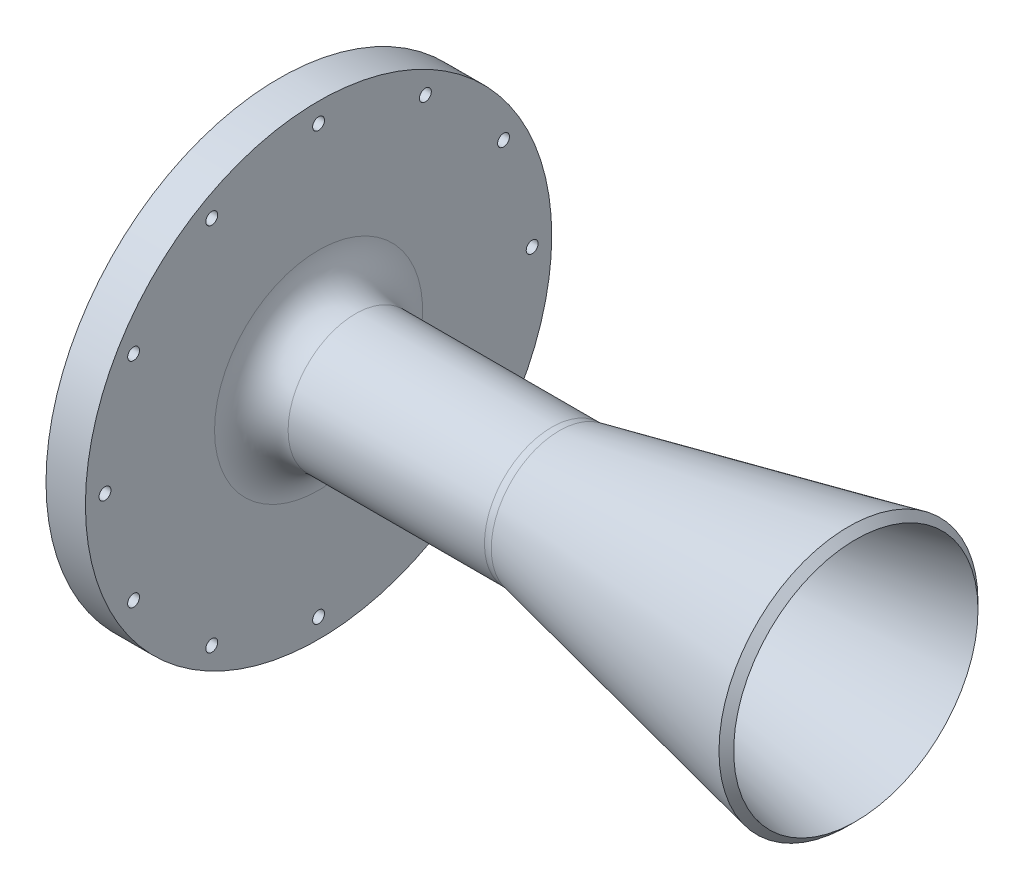
SolidWorks part; units mm, degrees
material "Stainless Steel (ferritic)"
ref_plane "Front Plane" through (0, 0, 0) normal (0, 0, 1) x (1, 0, 0)
ref_plane "Top Plane" through (0, 0, 0) normal (0, 1, 0) x (1, 0, 0)
ref_plane "Right Plane" through (0, 0, 0) normal (1, 0, 0) x (0, 0, -1)
sketch "Sketch2" plane through (0, 0, 0) normal (0, 0, 1) x (1, 0, 0)
  line L0 (0, 0) -> (165.0115, 0) construction
  line L1 (0, 20.5835) -> (0, 56.3562)
  line L2 (0, 56.3562) -> (9.525, 56.3562)
  line L3 (9.525, 56.3562) -> (9.525, 16.256)
  line L11 (66.8065, 16.256) -> (139.7, 31.75)
  line L17 (139.7, 31.75) -> (139.7, 29.5925)
  line L18 (60.325, 12.7208) -> (60.325, 14.351)
  line L19 (60.325, 14.351) -> (10.795, 14.351)
  line L20 (0, 20.5835) -> (10.795, 14.351)
  line L21 (60.325, 12.7208) -> (139.7, 29.5925)
  line L22 (9.525, 16.256) -> (66.8065, 16.256)
  dimension "D2" = 9.525
  dimension "D3" = 1.905
  dimension "D4" = 10.795
  dimension "D5" = 14.351
  dimension "D6" = 31.75
  dimension "D7" = 12
  dimension "D8" = 139.7
  dimension "D9" = 1.6302
  dimension "D10" = 30
  dimension "D11" = 56.3562
  dimension "D12" = 49.53
revolve "Main Structure" add sketch "Sketch2" angle 360 about L0
sketch "Sketch4" plane through (0, 0, 0) normal (-1, 0, 0) x (0, 0, 1)
  circle A0 centre (0, 0) radius 51.6255 construction
  circle A1 centre (0, -51.6255) radius 2.146
  circle A2 centre (-25.8127, -44.709) radius 2.146
  circle A3 centre (-44.709, -25.8128) radius 2.146
  circle A4 centre (-51.6255, 0) radius 2.146
  circle A5 centre (-44.709, 25.8127) radius 2.146
  circle A6 centre (-25.8128, 44.709) radius 2.146
  circle A7 centre (0, 51.6255) radius 2.146
  circle A8 centre (25.8127, 44.709) radius 2.146
  circle A9 centre (44.709, 25.8128) radius 2.146
  circle A10 centre (51.6255, 0) radius 2.146
  circle A11 centre (44.709, -25.8127) radius 2.146
  circle A12 centre (25.8128, -44.709) radius 2.146
  point P29 (0, 0)
  dimension "D1" = 12
  dimension "D2" = 103.251
hole_wizard "Flange Holes" positions "Sketch7" profile "Sketch8" hole size "#33" standard "ANSI Inch" end condition up to next
sketch "Sketch7" plane through (0, 0, 0) normal (-1, 0, 0) x (0, 0, 1)
  point P0 (0, -51.6255)
  point P3 (-25.8127, -44.709)
  point P6 (-44.709, -25.8128)
  point P9 (-51.6255, 0)
  point P12 (-44.709, 25.8127)
  point P15 (-25.8128, 44.709)
  point P18 (0, 51.6255)
  point P21 (25.8127, 44.709)
  point P24 (44.709, 25.8128)
  point P27 (51.6255, 0)
  point P30 (44.709, -25.8127)
  point P33 (25.8128, -44.709)
sketch "Sketch8" plane through (0, -51.6255, 0) normal (0, 1, 0) x (0, 0, 1)
  line L0 (0, 0) -> (0, 9.525)
  line L1 (0, 9.525) -> (1.4351, 9.525)
  line L2 (1.4351, 9.525) -> (1.4351, 0)
  line L5 (1.4351, 0) -> (0, 0)
  line L11 (0, -6.35) -> (0, 107.95) construction
  dimension "Thru Hole Dia." = 2.8702
  dimension "Thru Hole Depth" = 9.525
sketch "Sketch9" plane through (0, 0, 0) normal (-1, 0, 0) x (0, 0, 1)
  line L0 (0, 0) -> (-67.6727, 18.1329) construction
  line L1 (0, 0) -> (-51.6255, 0) construction
  circle A0 centre (0, 0) radius 51.6255 construction
  circle A1 centre (-49.8664, 13.3617) radius 2.9451
  circle A2 centre (49.8664, -13.3617) radius 2.9451
  point P14 (0, 0)
  dimension "D1" = 15
  dimension "D2" = 2
hole_wizard "Dowel Holes" positions "Sketch10" profile "Sketch11" hole size "3/16" standard "ANSI Inch"
sketch "Sketch10" plane through (0, 0, 0) normal (-1, 0, 0) x (0, 0, 1)
  point P0 (49.8664, -13.3617)
  point P3 (-49.8664, 13.3617)
sketch "Sketch11" plane through (0, -13.3617, 49.8664) normal (0, 1, 0) x (0, 0, 1)
  line L0 (0, 0) -> (0, 7.7808)
  line L1 (0, 7.7808) -> (2.3812, 6.35)
  line L2 (2.3812, 6.35) -> (2.3812, 0)
  line L5 (2.3812, 0) -> (0, 0)
  line L10 (0, 7.7808) -> (-2.3812, 6.35) construction
  line L11 (0, -6.35) -> (0, 107.95) construction
  dimension "Hole Dia." = 4.7625
  dimension "Hole Depth" = 6.35
  dimension "Drill Angle" = 118
fillet "Fillet1" radius 8.89 2 edges at (66.8065, 0, 16.256) (9.525, 0, 16.256)
sketch "Sketch13" plane through (0, 0, 0) normal (0, 1, 0) x (1, 0, 0)
  line L0 (0, 38.1) -> (3.3333, 0)
  line L1 (0, 56.3562) -> (0, -56.3562) construction
  line L2 (3.3333, 0) -> (0, 0)
  line L3 (0, 0) -> (0, 38.1)
  dimension "D1" = 38.1
  dimension "D2" = 5
revolve "Cut-Revolve1" cut sketch "Sketch13" angle 360 about L2
chamfer "Chamfer1" distance 2.54 angle 45 1 edges at (139.7, 0, 31.75) first distance on face at (139.7, 0, 31.75)
